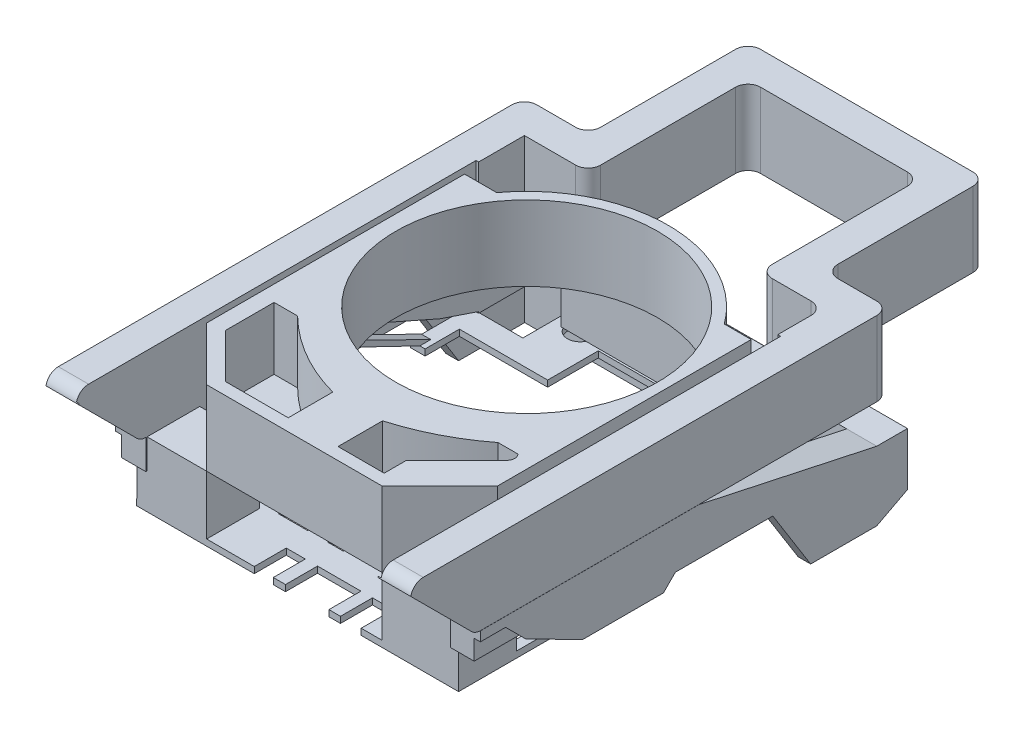
SolidWorks part; units mm, degrees
ref_plane "Front Plane" through (0, 0, 0) normal (0, 0, 1) x (1, 0, 0)
ref_plane "Top Plane" through (0, 0, 0) normal (0, 1, 0) x (1, 0, 0)
ref_plane "Right Plane" through (0, 0, 0) normal (1, 0, 0) x (0, 0, -1)
sketch "Sketch1" plane through (0, 0, 0) normal (0, 1, 0) x (1, 0, 0)
  line L0 (0, -25.6056) -> (-12, -25.6056) construction
  line L1 (0, 25.6056) -> (0, -25.6056) construction
  line L2 (6.8898, 25.6056) -> (-6.8898, 25.6056)
  line L3 (-12, -25.6056) -> (-14.64, -25.6056)
  line L4 (-12, -25.6056) -> (-12, 10.1444)
  line L5 (-12, 10.1444) -> (-14.64, 10.1444)
  line L6 (-14.64, -25.6056) -> (-14.64, 10.1444)
  line L7 (14.64, 10.1444) -> (14.64, 12.7744)
  line L8 (-6.8898, 25.6056) -> (6.8898, 25.6056)
  line L9 (-6.8898, 25.6056) -> (-6.8898, 22.9756)
  line L10 (-6.8898, 22.9756) -> (6.8898, 22.9756)
  line L11 (0, 25.6056) -> (0, 22.9756)
  line L12 (-6.8898, 25.6056) -> (-9.5198, 25.6056)
  line L13 (-6.8898, 25.6056) -> (-6.8898, 12.7744)
  line L14 (-6.8898, 12.7744) -> (-9.5198, 12.7744)
  line L15 (-9.5198, 25.6056) -> (-9.5198, 12.7744)
  line L16 (-14.64, 10.1444) -> (-6.8898, 10.1444)
  line L17 (-14.64, 10.1444) -> (-14.64, 12.7744)
  line L18 (-14.64, 12.7744) -> (-6.8898, 12.7744)
  line L19 (-6.8898, 10.1444) -> (-6.8898, 12.7744)
  line L20 (14.64, 10.1444) -> (6.8898, 10.1444)
  line L21 (14.64, -25.6056) -> (14.64, 10.1444)
  line L22 (12, 10.1444) -> (14.64, 10.1444)
  line L23 (12, -25.6056) -> (12, 10.1444)
  line L24 (12, -25.6056) -> (14.64, -25.6056)
  line L25 (6.8898, 10.1444) -> (6.8898, 12.7744)
  line L26 (14.64, 12.7744) -> (6.8898, 12.7744)
  line L27 (9.5198, 25.6056) -> (9.5198, 12.7744)
  line L28 (6.8898, 12.7744) -> (9.5198, 12.7744)
  line L29 (6.8898, 25.6056) -> (6.8898, 12.7744)
  line L30 (6.8898, 25.6056) -> (9.5198, 25.6056)
  line L31 (6.8898, 25.6056) -> (6.8898, 22.9756)
  point P0 (0, 0)
extrude "Boss-Extrude1" add sketch "Sketch1" along normal blind 6 contours L16 L19 L14 L18 L17 L5 | L6 L3 L4 L5 | L12 L15 L14 L13 L9 | L11 L8 L9 L10 | L29 L2 L11 L10 | L30 L29 L26 L27 | L7 L26 L25 L20 | L23 L24 L21 L20 region at (3.4449, 0, -24.2906) region at (8.2048, 0, -19.19) region at (-3.4449, 0, -24.2906) region at (-8.2048, 0, -19.19) region at (10.7649, 0, -11.4594) region at (-10.7649, 0, -11.4594) region at (13.32, 0, 7.7306) region at (-13.32, 0, 7.7306)
sketch "Sketch2" plane through (-14.64, 0, 0) normal (-1, 0, 0) x (0, 0, 1)
  line L0 (25.6056, 5.1591) -> (20.4465, 0)
  line L1 (25.6056, 6) -> (25.6056, 0) construction
  line L2 (25.6056, 0) -> (-12.7744, 0) construction
  line L3 (20.4465, 0) -> (25.6056, 0)
  line L4 (25.6056, 0) -> (25.6056, 5.1591)
extrude "Cut-Extrude1" cut sketch "Sketch2" against normal up to surface (29.28 mm away) contours L4 L0 L3 up to face at (14.64, 3, 6.4156)
fillet "Fillet1" radius 1 15 edges at (13.32, 6, 25.6056) (12, 3, -10.1444) (6.8898, 3, -10.1444) (6.8898, 3, -22.9756) (-6.8898, 3, -22.9756) (-6.8898, 3, -10.1444) (-13.32, 6, 25.6056) (-13.32, 0, 20.4465) (-14.64, 3, -12.7744) (-9.5198, 3, -12.7744) (-9.5198, 3, -25.6056) (13.32, 0, 20.4465) (14.64, 3, -12.7744) (9.5198, 3, -12.7744) (9.5198, 3, -25.6056)
sketch "Sketch3" plane through (14.64, 0, 0) normal (1, 0, 0) x (0, 0, -1)
  line L0 (-20.0323, 0) -> (-2.5323, 0)
  line L1 (-20.0323, 0) -> (11.7744, 0) construction
  line L2 (11.7744, 3) -> (11.7744, -10.8803) construction
  line L3 (11.7744, 0) -> (11.7744, 6) construction
  line L4 (-2.5323, 0) -> (11.7744, -3.084)
  line L5 (11.7744, -3.084) -> (14.2341, -3.084)
  line L6 (14.2341, -3.084) -> (14.2341, -7.334)
  line L7 (14.2341, -7.334) -> (11.7744, -8.6208)
  line L8 (11.7744, -8.6208) -> (6.4696, -8.6208)
  line L9 (6.4696, -8.6208) -> (3.4314, -3.7625)
  line L10 (3.4314, -3.7625) -> (-4.3867, -3.7625)
  line L11 (-4.3867, -3.7625) -> (-5.3452, -4.7211)
  line L12 (-5.3452, -4.7211) -> (-11.8452, -4.7211)
  line L13 (-20.0323, 0) -> (-20.0323, -2.37)
  line L14 (-20.0323, -2.37) -> (-16.4151, -2.37)
  line L15 (-16.4151, -2.37) -> (-11.8452, -4.7211)
extrude "Boss-Extrude2" add sketch "Sketch3" against normal up to vertex (29.28 mm away) up to point (-14.64, 0, 20.0323)
sketch "Sketch4" plane through (0, -8.6208, 0) normal (0, -1, 0) x (-1, 0, 0)
  line L0 (-14.64, 11.7744) -> (-13.64, 11.7744) construction
  line L1 (14.64, 11.7744) -> (-14.64, 11.7744) construction
  line L2 (14.64, 6.4696) -> (-14.64, 6.4696) construction
  line L3 (-13.64, 11.7744) -> (-12.2314, 11.7744)
  line L4 (-13.64, 11.7744) -> (-13.64, 6.4696)
  line L5 (-13.64, 6.4696) -> (-12.2314, 6.4696)
  line L6 (-12.2314, 11.7744) -> (-12.2314, 6.4696)
extrude "Cut-Extrude2" cut sketch "Sketch4" against normal blind 3.8
sketch "Sketch5" plane through (0, -8.6208, 0) normal (0, -1, 0) x (-1, 0, 0)
  line L0 (14.64, 11.7744) -> (-12.2314, 11.7744) construction
  line L1 (-12.2314, 6.4696) -> (-7.3314, 6.4696)
  line L2 (-12.2314, 6.4696) -> (-12.2314, 11.7744)
  line L3 (-12.2314, 11.7744) -> (-7.3314, 11.7744)
  line L4 (-7.3314, 6.4696) -> (-7.3314, 11.7744)
extrude "Cut-Extrude3" cut sketch "Sketch5" against normal up to next
sketch "Sketch6" plane through (0, -8.6208, 0) normal (0, -1, 0) x (-1, 0, 0)
  line L0 (14.64, 11.7744) -> (13.6092, 11.7744) construction
  line L1 (14.64, 11.7744) -> (-7.3314, 11.7744) construction
  line L2 (14.64, 6.4696) -> (-7.3314, 6.4696) construction
  line L3 (13.6092, 11.7744) -> (12.2092, 11.7744)
  line L4 (13.6092, 11.7744) -> (13.6092, 6.4696)
  line L5 (13.6092, 6.4696) -> (12.2092, 6.4696)
  line L6 (12.2092, 11.7744) -> (12.2092, 6.4696)
extrude "Cut-Extrude4" cut sketch "Sketch6" against normal blind 3.8
sketch "Sketch7" plane through (0, -8.6208, 0) normal (0, -1, 0) x (-1, 0, 0)
  line L1 (-7.3314, 11.7744) -> (12.2092, 11.7744)
  line L2 (-7.3314, 11.7744) -> (-7.3314, 6.4696)
  line L3 (-7.3314, 6.4696) -> (12.2092, 6.4696)
  line L4 (12.2092, 11.7744) -> (12.2092, 6.4696)
extrude "Cut-Extrude5" cut sketch "Sketch7" against normal up to next
sketch "Sketch9" plane through (0, -4.8208, 0) normal (0, -1, 0) x (1, 0, 0)
  line L1 (12.2314, -6.4696) -> (-12.2092, -6.4696)
  line L2 (12.2314, -6.4696) -> (12.2314, 25.5888)
  line L3 (12.2314, 25.5888) -> (-12.2092, 25.5888)
  line L4 (-12.2092, -6.4696) -> (-12.2092, 25.5888)
extrude "Cut-Extrude6" cut sketch "Sketch9" against normal through all both and the other way through all
sketch "Sketch10" plane through (12.2314, 0, 0) normal (-1, 0, 0) x (0, 0, 1)
  line L0 (-6.6685, -4.6032) -> (-3.6091, -3.5688)
  line L1 (-3.6091, -3.5688) -> (4.0108, -0.2081)
  line L2 (4.0108, -0.2081) -> (6.403, -0.2081)
  line L3 (6.403, -0.2081) -> (10.2326, -3.5688)
  line L4 (10.2326, -3.5688) -> (20.0323, -3.5688)
  line L5 (20.0323, -2.37) -> (20.0323, -5.3593) construction
  line L6 (20.0323, -2.37) -> (20.0323, 4.0236)
  line L7 (20.0323, 4.0236) -> (-6.6685, 4.0236)
  line L9 (-6.6685, 4.0236) -> (-6.6685, -4.6032)
  line L10 (20.0323, -3.5688) -> (19.043, -10.431)
  line L11 (19.043, -10.431) -> (-6.6685, -8.6067)
  line L12 (-6.6685, -8.6067) -> (-6.6685, -4.6032)
  line L13 (20.0323, -2.37) -> (20.0323, -3.5688)
  line M12 (-11.7744, -4.8208) -> (-6.4696, -4.8208)
  line M13 (-6.4696, -4.8208) -> (-6.4696, -8.6208)
  line M14 (-6.4696, -8.6208) -> (-3.4314, -3.7625)
  line M15 (-3.4314, -3.7625) -> (4.3867, -3.7625)
  line M16 (4.3867, -3.7625) -> (5.3452, -4.7211)
  line M17 (5.3452, -4.7211) -> (11.8452, -4.7211)
  line M18 (11.8452, -4.7211) -> (16.4151, -2.37)
extrude "Cut-Extrude15" cut sketch "Sketch10" against normal up to surface and the other way up to surface contours L11 L10 L4 M18 M17 M16 M15 M14 | L12 L4 L3 L2 L1 L0 M12 M13 M14 M15 M16 M17 M18 region at (12.2314, -3.1942, 3.5401) region at (12.2314, -6.8317, 7.8996) up to face at (13.64, -6.7208, -9.122) other way up to face at (-13.6092, -6.7208, -9.122)
sketch "Sketch11" plane through (14.64, 0, 0) normal (1, 0, 0) x (0, 0, -1)
  line L0 (-16.4151, -2.37) -> (-18.0068, -0.7783)
  line L1 (-18.0068, -0.7783) -> (-20.0323, -0.7783)
  line L2 (-20.0323, 0) -> (-20.0323, -2.37) construction
  line L3 (-20.0323, -0.7783) -> (-20.0323, -2.37)
  line L4 (-20.0323, -2.37) -> (-16.4151, -2.37)
extrude "Cut-Extrude16" cut sketch "Sketch11" against normal blind 0.5
sketch "Sketch12" plane through (-14.64, 0, 0) normal (-1, 0, 0) x (0, 0, 1)
  line L0 (20.0323, -0.7783) -> (20.0323, -2.37)
  line L1 (20.0323, -2.37) -> (16.4151, -2.37)
  line L2 (16.4151, -2.37) -> (18.0068, -0.7783)
  line L3 (18.0068, -0.7783) -> (20.0323, -0.7783)
extrude "Cut-Extrude17" cut sketch "Sketch12" against normal blind 0.5
sketch "Sketch13" plane through (14.64, 0, 0) normal (1, 0, 0) x (0, 0, -1)
  line L0 (-20.0323, 0) -> (-20.0323, -0.7783) construction
  line L1 (-2.5305, 0.0032) -> (-20.0323, 0.0032)
  line L2 (-2.5305, 0.0032) -> (-2.5305, -0.013)
  line L3 (-2.5305, -0.013) -> (-20.0323, -0.013)
  line L4 (-20.0323, 0.0032) -> (-20.0323, -0.013)
extrude "Cut-Extrude19" cut sketch "Sketch13" against normal blind 0.01
sketch "Sketch14" plane through (-14.64, 0, 0) normal (-1, 0, 0) x (0, 0, 1)
  line L1 (2.5318, 0.0004) -> (20.415, 0.0004)
  line L2 (2.5318, 0.0004) -> (2.5318, 0.0761)
  line L3 (2.5318, 0.0761) -> (20.415, 0.0761)
  line L4 (20.415, 0.0004) -> (20.415, 0.0761)
  arc A0 (20.0323, 0) -> (20.7394, 0.2929) centre (20.0323, 1) ccw construction
extrude "Cut-Extrude20" cut sketch "Sketch14" against normal blind 0.01
sketch "Sketch15" plane through (0, 6, 0) normal (0, 1, 0) x (1, 0, 0)
  line L0 (-14.6541, -1.6608) -> (14.6259, -1.6608) construction
  line L1 (-8.0787, 5.0631) -> (11.2728, 5.0631)
  line L3 (-8.0787, 5.0631) -> (-11.7227, 5.0631)
  line L4 (-11.7227, 5.0631) -> (-11.7227, -15.632)
  line L5 (-11.7227, -15.632) -> (-7.4323, -19.9224)
  line L6 (-7.4323, -19.9224) -> (6.6474, -19.9224)
  line L7 (6.6474, -19.9224) -> (11.2728, -15.2969)
  line L8 (11.2728, -15.2969) -> (11.2728, 5.0631)
  circle A0 centre (-0.0141, -1.6608) radius 10.5
  circle A1 centre (-0.0141, -1.6608) radius 11.3411
extrude "Boss-Extrude3" add sketch "Sketch15" against normal blind 6.01 separate body contours A1 L0 A0 L3 | L1 A1 L3 A0 | A0 L0 L8 A1 L1 | L0 A1 L8 A0 | L0 L4 L5 L6 L7 L8 A1 | L4 L0 A1 L3 | A1 L8 L1 region at (-10.9911, 6, -2.8287) region at (-0.5076, 6, 14.4267) region at (-10.1495, 6, -1.8304) region at (-10.9346, 6, 1.9139) region at (-0.0141, 6, -9.4919) region at (10.1136, 6, -1.8508) region at (10.6315, 6, -3.516)
sketch "Sketch16" plane through (0, 6, 0) normal (0, 1, 0) x (1, 0, 0)
  line L0 (-10.4505, -15.373) -> (-6.8762, -18.9472)
  line L1 (-6.8762, -18.9472) -> (-1.8621, -18.9472)
  line L2 (-1.8621, -18.9472) -> (-1.8621, -15.373)
  line L3 (-10.4505, -15.373) -> (-10.4505, -11.4954)
  line L4 (-10.4505, -11.4954) -> (-8.56, -11.4954)
  line L5 (2.1327, -18.9472) -> (2.1327, -15.373)
  line L6 (2.1327, -18.9472) -> (5.8368, -18.9472)
  line L7 (5.8368, -18.9472) -> (5.8368, -17.1601)
  line L8 (5.8368, -17.1601) -> (9.8708, -13.1261)
  line L9 (9.8708, -12.2496) -> (8.2771, -12.2496)
  arc A1 (-8.56, -11.4954) -> (-1.8621, -15.373) centre (2.1327, -0.749) ccw
  arc A2 (9.8708, -13.1261) -> (9.8708, -12.2496) centre (9.4326, -12.6878) ccw
  arc A3 (8.2771, -12.2496) -> (2.1327, -15.373) centre (-2.9633, 2.2573) cw
extrude "Cut-Extrude21" cut sketch "Sketch16" against normal blind 5
sketch "Sketch17" plane through (0, -0.01, 0) normal (0, -1, 0) x (1, 0, 0)
  line L1 (6.6474, 19.9224) -> (12.782, 19.9224)
  line L2 (6.6474, 19.9224) -> (6.6474, 15.2826)
  line L3 (6.6474, 15.2826) -> (12.782, 15.2826)
  line L4 (12.782, 19.9224) -> (12.782, 15.2826)
  line L5 (-7.4323, 19.9224) -> (-13.0049, 19.9224)
  line L6 (-7.4323, 19.9224) -> (-7.4323, 15.7023)
  line L7 (-7.4323, 15.7023) -> (-13.0049, 15.7023)
  line L8 (-13.0049, 19.9224) -> (-13.0049, 15.7023)
extrude "Boss-Extrude4" add sketch "Sketch17" along normal up to vertex (4.7111 mm away) up to point (14.64, -4.7211, 11.8452)
sketch "Sketch18" plane through (0, -0.01, 0) normal (0, -1, 0) x (1, 0, 0)
  line L1 (7.8898, -11.1444) -> (-7.9402, -11.1444)
  line L2 (7.8898, -11.1444) -> (7.8898, -9.0311)
  line L3 (7.8898, -9.0311) -> (-7.9402, -9.0311)
  line L4 (-7.9402, -11.1444) -> (-7.9402, -9.0311)
extrude "Boss-Extrude5" add sketch "Sketch18" along normal up to surface (4.7111 mm away) up to face at (9.7147, -4.7211, 17.6025)
sketch "Sketch19" plane through (0, -4.7211, 0) normal (0, -1, 0) x (-1, 0, 0)
  line L1 (-12.782, -19.9224) -> (13.0544, -19.9224)
  line L2 (-12.782, -19.9224) -> (-12.782, -10.1624)
  line L3 (-12.782, -10.1624) -> (13.0544, -10.1624)
  line L4 (13.0544, -19.9224) -> (13.0544, -10.1624)
extrude "Boss-Extrude6" add sketch "Sketch19" along normal blind 0.5 separate body
sketch "Sketch20" plane through (0, -5.2211, 0) normal (0, -1, 0) x (-1, 0, 0)
  line L0 (13.0544, -10.1624) -> (-12.782, -10.1624) construction
  line L1 (-4.966, -17.3552) -> (-3.3066, -17.3552)
  line L2 (-4.966, -17.3552) -> (-4.966, -20.7621)
  line L3 (-4.966, -20.7621) -> (-3.3066, -20.7621)
  line L4 (-3.3066, -17.3552) -> (-3.3066, -20.7621)
  line L5 (-2.3787, -17.3552) -> (1.1049, -17.3552)
  line L6 (-2.3787, -17.3552) -> (-2.3787, -20.7621)
  line L7 (-2.3787, -20.7621) -> (1.1049, -20.7621)
  line L8 (1.1049, -17.3552) -> (1.1049, -20.7621)
  line L9 (2.085, -17.3552) -> (3.6108, -17.3552)
  line L10 (2.085, -17.3552) -> (2.085, -20.7621)
  line L11 (2.085, -20.7621) -> (3.6108, -20.7621)
  line L12 (3.6108, -17.3552) -> (3.6108, -20.7621)
  line L13 (-11.9503, -16.1274) -> (-10.6389, -16.1274)
  line L14 (-11.9503, -16.1274) -> (-11.9503, -10.1624)
  line L15 (-11.9503, -10.1624) -> (-10.6389, -10.1624)
  line L16 (-10.6389, -16.1274) -> (-10.6389, -10.1624)
  line L18 (-7.0011, -12.3238) -> (-4.966, -12.3238)
  line L19 (-7.0011, -12.3238) -> (-7.0011, -15.2858)
  line L20 (-7.0011, -15.2858) -> (-4.966, -15.2858)
  line L21 (-4.966, -12.3238) -> (-4.966, -15.2858)
  line L22 (-3.7344, -15.2858) -> (-2.3787, -15.2858)
  line L23 (-3.7344, -15.2858) -> (-3.7344, -9.3648)
  line L24 (-3.7344, -9.3648) -> (-2.3787, -9.3648)
  line L25 (-2.3787, -15.2858) -> (-2.3787, -9.3648)
  line L26 (1.1049, -15.2858) -> (2.3724, -15.2858)
  line L27 (1.1049, -15.2858) -> (1.1049, -9.3648)
  line L28 (1.1049, -9.3648) -> (2.3724, -9.3648)
  line L29 (2.3724, -15.2858) -> (2.3724, -9.3648)
  line L30 (3.9495, -12.6627) -> (6.3053, -12.6627)
  line L31 (3.9495, -12.6627) -> (3.9495, -15.2858)
  line L32 (3.9495, -15.2858) -> (6.3053, -15.2858)
  line L33 (6.3053, -12.6627) -> (6.3053, -15.2858)
  line L34 (12.2994, -10.1624) -> (11.0971, -10.1624)
  line L35 (12.2994, -10.1624) -> (12.2994, -15.2858)
  line L36 (12.2994, -15.2858) -> (11.0971, -15.2858)
  line L37 (11.0971, -10.1624) -> (11.0971, -15.2858)
  line L38 (-10.6389, -10.1624) -> (11.0971, -10.1624)
  line L39 (-10.6389, -10.1624) -> (-10.6389, -11.5988)
  line L40 (-10.6389, -11.5988) -> (11.0971, -11.5988)
  line L41 (11.0971, -10.1624) -> (11.0971, -11.5988)
  line L42 (-2.3787, -11.5988) -> (1.1049, -11.5988)
  line L43 (-2.3787, -11.5988) -> (-2.3787, -13.4475)
  line L44 (-2.3787, -13.4475) -> (1.1049, -13.4475)
  line L45 (1.1049, -11.5988) -> (1.1049, -13.4475)
  circle A0 centre (-11.0897, -18.466) radius 1.1108
  circle A1 centre (11.3936, -18.466) radius 1.1017
  line M9 (13.0544, -10.1624) -> (-12.782, -10.1624)
extrude "Cut-Extrude22" cut sketch "Sketch20" against normal up to next (0.5 mm away) contours A0 | L21 L18 L19 L20 | L40 L27 L26 L29 | L33 L30 L31 L32 | L37 L36 L35 M9 | A1 | L14 L15 L16 L13 | L40 L41 L38 L39 | L25 L24 L23 L22 | L28 L29 L26 L27 | L1 L4 L3 L2 | L5 L8 L7 L6 | L9 L12 L11 L10 | L43 L42 L45 L44 region at (-1.7387, -5.2211, 13.4423) region at (-11.6982, -5.2211, 12.7241) region at (5.9836, -5.2211, 13.8048) region at (-5.1274, -5.2211, 13.9742) region at (11.0897, -5.2211, 18.466) region at (-11.3936, -5.2211, 18.466)
sketch "Sketch21" plane through (11.9503, 0, 0) normal (-1, 0, 0) x (0, 0, 1)
  line L0 (10.1624, -4.7211) -> (6.4105, -1.2192)
  line L2 (6.4105, -1.2192) -> (4.168, -1.2192)
  line L3 (4.168, -1.2192) -> (-2.9293, -4.7211)
  line L4 (10.1624, -4.7211) -> (10.1624, -5.2211) construction
  line L5 (10.1624, -5.2211) -> (6.34, -1.6467)
  line L6 (6.34, -1.6467) -> (4.168, -1.7195)
  line L7 (4.168, -1.7195) -> (-2.0513, -4.7211)
  line L8 (-2.0513, -4.7211) -> (-2.9293, -4.7211)
  line L9 (10.1624, -4.7211) -> (10.1624, -5.2211)
extrude "Boss-Extrude7" add sketch "Sketch21" against normal up to vertex (0.8318 mm away) and the other way up to vertex (25.0047 mm away) up to point (12.782, -4.7211, 10.1624) other way up to point (-13.0544, -4.7211, 10.1624)
sketch "Sketch22" plane through (0, -5.2211, 0) normal (0, -1, 0) x (-1, 0, 0)
  line L1 (-11.9503, -10.1624) -> (12.2994, -10.1624)
  line L2 (-11.9503, -10.1624) -> (-11.9503, 3.1037)
  line L3 (-11.9503, 3.1037) -> (12.2994, 3.1037)
  line L4 (12.2994, -10.1624) -> (12.2994, 3.1037)
extrude "Cut-Extrude23" cut sketch "Sketch22" against normal up to next
sketch "Sketch25" plane through (0, -4.7211, 0) normal (0, -1, 0) x (-1, 0, 0)
  line L1 (-12.782, 2.0513) -> (13.0402, 2.0513)
  line L2 (-12.782, 2.0513) -> (-12.782, 11.1528)
  line L3 (-12.782, 11.1528) -> (13.0402, 11.1528)
  line L4 (13.0402, 2.0513) -> (13.0402, 11.1528)
extrude "Boss-Extrude10" add sketch "Sketch25" along normal up to surface (0.5 mm away) up to face at (-11.3936, -5.2211, 17.3644)
sketch "Sketch26" plane through (0, -5.2211, 0) normal (0, -1, 0) x (-1, 0, 0)
  line L0 (0.1291, 2.0513) -> (0.1291, 11.1528) construction
  line L1 (-12.782, 2.0513) -> (-11.6195, 2.0513)
  line L2 (-12.782, 2.0513) -> (-12.782, 6.7321)
  line L3 (-12.782, 6.7321) -> (-11.6195, 6.7321)
  line L4 (-11.6195, 2.0513) -> (-11.6195, 6.7321)
  line L5 (-12.782, 6.7321) -> (-4.5406, 6.7321)
  line L6 (-12.782, 6.7321) -> (-12.782, 4.8035)
  line L7 (-12.782, 4.8035) -> (-4.5406, 4.8035)
  line L8 (-4.5406, 6.7321) -> (-4.5406, 4.8035)
  line L9 (13.0402, 2.0513) -> (-12.782, 2.0513) construction
  line L10 (-12.782, 11.1528) -> (13.0402, 11.1528) construction
  line L11 (4.7988, 11.1528) -> (4.7988, 8.8661)
  line L12 (-4.5406, 4.8035) -> (-8.4564, 4.8035)
  line L13 (-4.5406, 4.8035) -> (-4.5406, 11.1528)
  line L14 (-4.5406, 11.1528) -> (-8.4564, 11.1528)
  line L15 (-8.4564, 4.8035) -> (-8.4564, 11.1528)
  line L16 (-4.5406, 11.1528) -> (4.7988, 11.1528)
  line L17 (-4.5406, 11.1528) -> (-4.5406, 8.8661)
  line L18 (-4.5406, 8.8661) -> (4.7988, 8.8661)
  line L19 (0.1291, 11.1528) -> (0.1291, 8.8661)
  line L20 (8.7146, 4.8035) -> (8.7146, 11.1528)
  line L21 (4.7988, 11.1528) -> (8.7146, 11.1528)
  line L22 (4.7988, 4.8035) -> (4.7988, 11.1528)
  line L23 (4.7988, 4.8035) -> (8.7146, 4.8035)
  line L24 (4.7988, 6.7321) -> (4.7988, 4.8035)
  line L25 (13.0402, 4.8035) -> (4.7988, 4.8035)
  line L26 (13.0402, 6.7321) -> (13.0402, 4.8035)
  line L27 (13.0402, 6.7321) -> (4.7988, 6.7321)
  line L28 (11.8776, 2.0513) -> (11.8776, 6.7321)
  line L29 (13.0402, 6.7321) -> (11.8776, 6.7321)
  line L30 (13.0402, 2.0513) -> (13.0402, 6.7321)
  circle A0 centre (-6.6135, 9.4873) radius 1.0229
  circle A1 centre (6.8716, 9.4873) radius 1.0229
  line M15 (-12.782, 2.0513) -> (13.0402, 2.0513)
  line M16 (13.0402, 2.0513) -> (13.0402, 11.1528)
  line M17 (13.0402, 11.1528) -> (-12.782, 11.1528)
  line M18 (-12.782, 11.1528) -> (-12.782, 2.0513)
extrude "Cut-Extrude25" cut sketch "Sketch26" against normal blind 0.5 contours L5 L15 L3 M17 M18 | L0 L18 L13 L8 L7 L4 M15 | L0 L28 L25 L23 L22 L18 M15 | A1 | A0 | L27 L20 M16 M17 region at (4.4364, -5.2211, -4.6874) region at (-4.6946, -5.2211, -4.6874) region at (10.6192, -5.2211, -8.9424) region at (-10.8774, -5.2211, -8.9424) region at (6.6135, -5.2211, -9.4873) region at (-6.8716, -5.2211, -9.4873)
